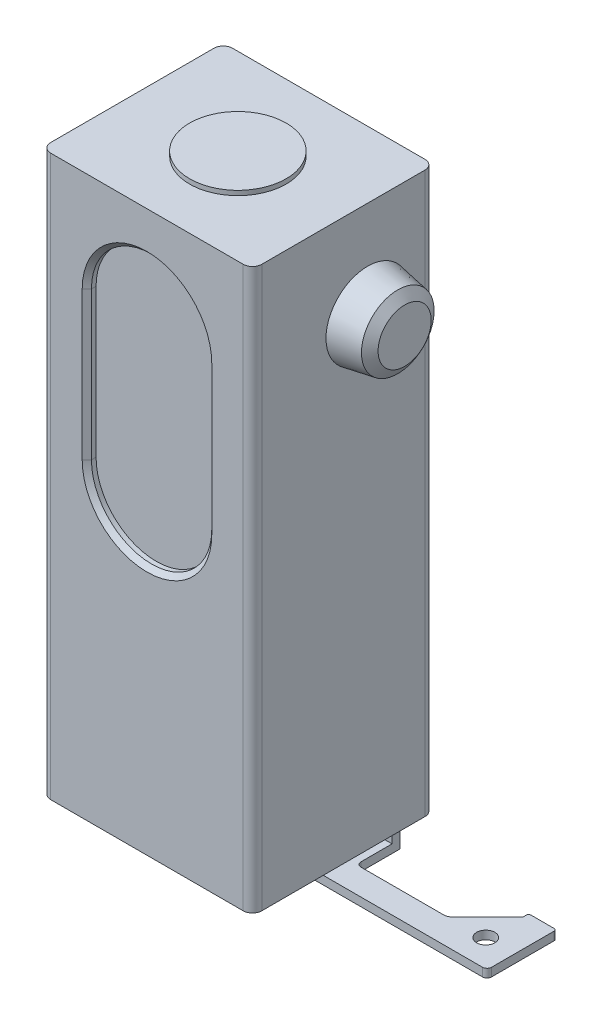
SolidWorks part; units mm, degrees
ref_plane "Front Plane" through (0, 0, 0) normal (0, 0, 1) x (1, 0, 0)
ref_plane "Top Plane" through (0, 0, 0) normal (0, 1, 0) x (1, 0, 0)
ref_plane "Right Plane" through (0, 0, 0) normal (1, 0, 0) x (0, 0, -1)
sketch "Sketch1" plane through (0, 0, 0) normal (0, 1, 0) x (1, 0, 0)
  line L1 (-28.956, -24.9428) -> (28.956, -24.9428)
  line L2 (-28.956, -24.9428) -> (-28.956, 24.9428)
  line L3 (-28.956, 24.9428) -> (28.956, 24.9428)
  line L4 (28.956, -24.9428) -> (28.956, 24.9428)
  line L5 (-28.956, -24.9428) -> (28.956, 24.9428) construction
  line L6 (-28.956, 24.9428) -> (28.956, -24.9428) construction
  point P0 (0, 0)
  dimension "D1" = 49.8856
  dimension "D2" = 57.912
extrude "Boss-Extrude1" add sketch "Sketch1" along normal blind 153.67
shell "Shell2" thickness 2.54 removed face at (0, 153.67, 0)
sketch "Sketch2" plane through (0, 153.67, 0) normal (0, 1, 0) x (1, 0, 0)
  line L1 (-26.416, -22.4028) -> (26.416, -22.4028)
  line L2 (-26.416, -22.4028) -> (-26.416, 22.4028)
  line L3 (-26.416, 22.4028) -> (26.416, 22.4028)
  line L4 (26.416, -22.4028) -> (26.416, 22.4028)
  line L5 (-26.416, -22.4028) -> (26.416, 22.4028) construction
  line L6 (-26.416, 22.4028) -> (26.416, -22.4028) construction
  point P0 (0, 0)
extrude "Boss-Extrude2" add sketch "Sketch2" against normal blind 2.54
sketch "Sketch3" plane through (0, 0, 24.9428) normal (0, 0, 1) x (1, 0, 0)
  line L0 (0, 85.09) -> (0, 125.73) construction
  line L1 (-16.51, 85.09) -> (-16.51, 125.73)
  line L2 (16.51, 85.09) -> (16.51, 125.73)
  line L3 (-28.956, 153.67) -> (28.956, 153.67) construction
  arc A0 (-16.51, 85.09) -> (16.51, 85.09) centre (0, 85.09) ccw
  arc A1 (16.51, 125.73) -> (-16.51, 125.73) centre (0, 125.73) ccw
  point P3 (0, 105.41)
  point P10 (0, 153.67)
  dimension "D2" = 16.51
  dimension "D1" = 40.64
  dimension "D3" = 27.94
extrude "Cut-Extrude1" cut sketch "Sketch3" against normal up to next
sketch "Sketch4" plane through (0, 0, 22.4028) normal (0, 0, -1) x (-1, 0, 0)
  line L20 (19.05, 85.09) -> (19.05, 125.73)
  line L21 (-19.05, 125.73) -> (-19.05, 85.09)
  line L22 (19.05, 85.09) -> (19.05, 125.73)
  line L23 (-19.05, 125.73) -> (-19.05, 85.09)
  arc A6 (-19.05, 85.09) -> (19.05, 85.09) centre (0, 85.09) ccw
  arc A7 (19.05, 125.73) -> (-19.05, 125.73) centre (0, 125.73) ccw
  arc A8 (-19.05, 85.09) -> (19.05, 85.09) centre (0, 85.09) ccw
  arc A9 (19.05, 125.73) -> (-19.05, 125.73) centre (0, 125.73) ccw
  dimension "D2" = 2.54
extrude "Boss-Extrude3" add sketch "Sketch4" along normal blind 2.54
sketch "Sketch5" plane through (0, 0, -24.9428) normal (0, 0, -1) x (-1, 0, 0)
  line L0 (-28.956, 0) -> (28.956, 0) construction
  line L1 (-17.3736, -13.5382) -> (17.3736, -13.5382)
  line L2 (-17.3736, -13.5382) -> (-17.3736, 97.536)
  line L3 (-17.3736, 97.536) -> (17.3736, 97.536)
  line L4 (17.3736, -13.5382) -> (17.3736, 97.536)
  line L5 (-17.3736, -13.5382) -> (17.3736, 97.536) construction
  line L6 (-17.3736, 97.536) -> (17.3736, -13.5382) construction
  point P0 (0, 41.9989)
  point P5 (0, 97.536)
  dimension "D1" = 34.7472
  dimension "D2" = 111.0742
  dimension "D3" = 97.536
extrude "Boss-Extrude4" add sketch "Sketch5" along normal blind 2.1336
sketch "Sketch6" plane through (0, 0, -27.0764) normal (0, 0, -1) x (-1, 0, 0)
  line L0 (-17.3736, 97.536) -> (-17.3736, -13.5382) construction
  line L1 (17.3736, 97.536) -> (-17.3736, 97.536) construction
  line L2 (0, 99.6626) -> (0, 70.4261) construction
  circle A0 centre (-11.0236, 91.186) radius 4.5212
  circle A1 centre (-11.0236, 78.486) radius 4.5212
  circle A2 centre (11.0236, 91.186) radius 4.5212
  circle A3 centre (11.0236, 78.486) radius 4.5212
  dimension "D1" = 9.0424
  dimension "D2" = 6.35
  dimension "D3" = 6.35
  dimension "D4" = 12.7
extrude "Boss-Extrude5" add sketch "Sketch6" along normal blind 9.2456
fillet "Fillet1" radius 1.27 4 edges at (6.5024, 78.486, -36.322) (-6.5024, 78.486, -36.322) (-6.5024, 91.186, -36.322) (6.5024, 91.186, -36.322)
chamfer "Chamfer1" distance 0.762 angle 45 4 edges at (15.5448, 91.186, -27.0764) (15.5448, 78.486, -27.0764) (-6.5024, 78.486, -27.0764) (-6.5024, 91.186, -27.0764)
fillet "Fillet2" radius 2.54 4 edges at (-28.956, 76.835, 24.9428) (-28.956, 76.835, -24.9428) (28.956, 76.835, -24.9428) (28.956, 76.835, 24.9428)
sketch "Sketch7" plane through (0, -13.5382, 0) normal (0, -1, 0) x (1, 0, 0)
  line L0 (0, 4.9688) -> (0, -36.0312) construction
  line L1 (1.27, -8.0264) -> (59.0804, -8.0264)
  line L2 (60.3504, -9.2964) -> (60.3504, -26.4414)
  line L3 (59.7154, -27.0764) -> (53.3654, -27.0764)
  line L4 (52.7304, -26.4414) -> (52.7304, -25.7793)
  line L5 (52.5444, -25.3303) -> (43.0965, -15.8823)
  line L6 (41.3004, -15.1384) -> (18.6436, -15.1384)
  line L7 (17.3736, -16.4084) -> (17.3736, -27.0764)
  line L8 (17.3736, -27.0764) -> (-17.3736, -27.0764) construction
  line L9 (17.3736, -27.0764) -> (-17.3736, -27.0764)
  line L10 (-17.3736, -16.4084) -> (-17.3736, -27.0764)
  line L11 (-41.3004, -15.1384) -> (-18.6436, -15.1384)
  line L12 (17.3736, -27.0764) -> (17.3736, -24.9428) construction
  line L13 (-52.5444, -25.3303) -> (-43.0965, -15.8823)
  line L14 (-52.7304, -26.4414) -> (-52.7304, -25.7793)
  line L15 (-59.7154, -27.0764) -> (-53.3654, -27.0764)
  line L16 (-60.3504, -9.2964) -> (-60.3504, -26.4414)
  line L17 (-1.27, -8.0264) -> (-59.0804, -8.0264)
  arc A0 (1.27, -8.0264) -> (0, -9.2964) centre (1.27, -9.2964) ccw
  arc A1 (59.0804, -8.0264) -> (60.3504, -9.2964) centre (59.0804, -9.2964) cw
  arc A2 (53.3654, -27.0764) -> (52.7304, -26.4414) centre (53.3654, -26.4414) cw
  arc A3 (60.3504, -26.4414) -> (59.7154, -27.0764) centre (59.7154, -26.4414) cw
  arc A4 (43.0965, -15.8823) -> (41.3004, -15.1384) centre (41.3004, -17.6784) ccw
  arc A5 (52.7304, -25.7793) -> (52.5444, -25.3303) centre (52.0954, -25.7793) ccw
  arc A6 (18.6436, -15.1384) -> (17.3736, -16.4084) centre (18.6436, -16.4084) ccw
  arc A7 (-18.6436, -15.1384) -> (-17.3736, -16.4084) centre (-18.6436, -16.4084) cw
  arc A8 (-43.0965, -15.8823) -> (-41.3004, -15.1384) centre (-41.3004, -17.6784) cw
  arc A9 (-52.7304, -25.7793) -> (-52.5444, -25.3303) centre (-52.0954, -25.7793) cw
  arc A10 (-53.3654, -27.0764) -> (-52.7304, -26.4414) centre (-53.3654, -26.4414) ccw
  arc A11 (-60.3504, -26.4414) -> (-59.7154, -27.0764) centre (-59.7154, -26.4414) ccw
  arc A12 (-59.0804, -8.0264) -> (-60.3504, -9.2964) centre (-59.0804, -9.2964) ccw
  arc A13 (-1.27, -8.0264) -> (0, -9.2964) centre (-1.27, -9.2964) cw
  point P34 (0, -27.0764)
  dimension "D1" = 1.27
  dimension "D2" = 1.27
  dimension "D3" = 0.635
  dimension "D4" = 2.54
  dimension "D5" = 0.635
  dimension "D6" = 1.27
  dimension "D7" = 60.3504
  dimension "D8" = 7.62
  dimension "D9" = 7.112
  dimension "D10" = 19.05
  dimension "D11" = 19.05
  dimension "D12" = 45
extrude "Boss-Extrude6" add sketch "Sketch7" along normal blind 2.3114
sketch "Sketch8" plane through (0, -15.8496, 0) normal (0, -1, 0) x (1, 0, 0)
  line L0 (0, 8.0498) -> (0, -46.6591) construction
  line L1 (-1.27, -8.0264) -> (-59.0804, -8.0264) construction
  circle A0 centre (-52.5, -15.5264) radius 2.5
  circle A1 centre (52.5, -15.5264) radius 2.5
  dimension "D1" = 5
  dimension "D2" = 52.5
  dimension "D3" = 7.5
extrude "Cut-Extrude2" cut sketch "Sketch8" against normal up to next
sketch "Sketch9" plane through (0, 153.67, 0) normal (0, 1, 0) x (1, 0, 0)
  circle A0 centre (0, 0) radius 13.25
  dimension "D1" = 26.5
extrude "Boss-Extrude7" add sketch "Sketch9" along normal blind 1.27
sketch "Sketch10" plane through (28.956, 0, 0) normal (1, 0, 0) x (0, 0, -1)
  line L0 (24.9428, 153.67) -> (24.9428, 0) construction
  line L2 (-22.4028, 153.67) -> (22.4028, 153.67) construction
  circle A0 centre (6.6548, 127.254) radius 11.43
  dimension "D1" = 22.86
  dimension "D2" = 18.288
  dimension "D3" = 26.416
extrude "Boss-Extrude8" add sketch "Sketch10" along normal blind 10.16 draft 10 contours A0
sketch "Sketch11" plane through (-28.956, 0, 0) normal (-1, 0, 0) x (0, 0, 1)
  line L0 (-24.9428, 0) -> (-24.9428, 153.67) construction
  line L1 (-22.4028, 153.67) -> (22.4028, 153.67) construction
  circle A0 centre (-7.1628, 127.508) radius 11.43
  circle A1 centre (-7.1628, 71.628) radius 11.43
  dimension "D3" = 22.86
  dimension "D1" = 17.78
  dimension "D2" = 26.162
  dimension "D4" = 55.88
extrude "Boss-Extrude9" add sketch "Sketch11" along normal blind 6.096 draft 10
chamfer "Chamfer2" distance 1.905 angle 45 3 edges at (-35.052, 71.628, 3.1923) (-35.052, 127.508, 3.1923) (39.116, 127.254, -16.2933) first distance on face at (-35.052, 71.628, 3.1923) first distance on face at (-35.052, 127.508, 3.1923) first distance on face at (39.116, 127.254, -16.2933)
chamfer "Chamfer3" distance 1.27 angle 45 4 edges at (-16.51, 105.41, 24.9428) (0, 68.58, 24.9428) (0, 142.24, 24.9428) (16.51, 105.41, 24.9428)
